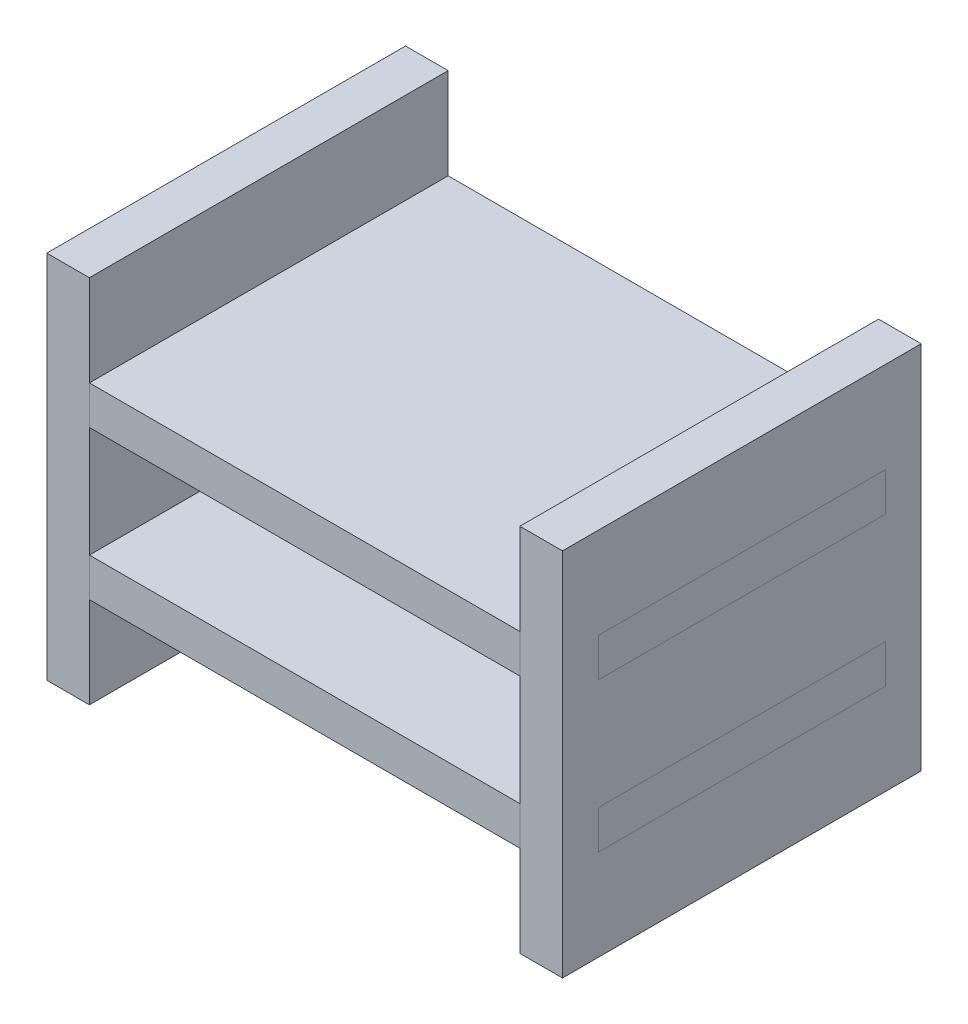
SolidWorks part; units mm, degrees
ref_plane "Front" through (0, 0, 0) normal (0, 0, 1) x (1, 0, 0)
ref_plane "Top" through (0, 0, 0) normal (0, 1, 0) x (1, 0, 0)
ref_plane "Right" through (0, 0, 0) normal (1, 0, 0) x (0, 0, -1)
sketch "Sketch2" plane through (0, 0, 0) normal (0, 1, 0) x (1, 0, 0)
  line L1 (-15, 12.5) -> (15, 12.5)
  line L2 (-15, 12.5) -> (-15, -12.5)
  line L3 (-15, -12.5) -> (15, -12.5)
  line L4 (15, 12.5) -> (15, -12.5)
  line L5 (-15, 12.5) -> (15, -12.5) construction
  line L6 (-15, -12.5) -> (15, 12.5) construction
  line L7 (-15, 10) -> (-17.97, 10)
  line L8 (-15, 10) -> (-15, -10)
  line L9 (-15, -10) -> (-17.97, -10)
  line L10 (-17.97, 10) -> (-17.97, -10)
  line L11 (-15, 10) -> (-17.97, -10) construction
  line L12 (-15, -10) -> (-17.97, 10) construction
  line L13 (15, 10) -> (17.97, 10)
  line L14 (15, 10) -> (15, -10)
  line L15 (15, -10) -> (17.97, -10)
  line L16 (17.97, 10) -> (17.97, -10)
  line L17 (15, 10) -> (17.97, -10) construction
  line L18 (15, -10) -> (17.97, 10) construction
  point P4 (0, 0)
  point P11 (-16.485, 0)
  point P16 (16.485, 0)
  dimension "D1" = 2.97
  dimension "D2" = 30
  dimension "D3" = 25
  dimension "D4" = 20
extrude "Boss-Extrude3" add sketch "Sketch2" along normal blind 2.69 contours L4 L1 L2 L3 | L7 L10 L9 L2 | L16 L13 L4 L15 region at (0, 0, 0) region at (-16.485, 0, 0) region at (16.485, 0, 0)
extrude "Boss-Extrude4" add sketch "Sketch2<3>" along normal blind 2.69 from offset 10.39 separate body contours L7 L10 L9 L2 | L4 L1 L2 L3 | L16 L13 L4 L15 region at (0, 0, 0) region at (-16.485, 0, 0) region at (16.485, 0, 0)
sketch "Sketch2<3>" plane through (0, 0, 0) normal (0, 1, 0) x (1, 0, 0) same geometry as "Sketch2"
sketch "Sketch4" plane through (15, 0, 0) normal (1, 0, 0) x (0, 0, -1)
  line L0 (0, 50) -> (0, -50) construction
  line L1 (12.5, -6.35) -> (-12.5, -6.35)
  line L2 (12.5, -6.35) -> (12.5, 19.43)
  line L3 (12.5, 19.43) -> (-12.5, 19.43)
  line L4 (-12.5, -6.35) -> (-12.5, 19.43)
  line L5 (12.5, -6.35) -> (-12.5, 19.43) construction
  line L6 (12.5, 19.43) -> (-12.5, -6.35) construction
  line L7 (-12.5, 13.08) -> (-12.5, 10.39) construction
  line L8 (-10, 13.08) -> (-12.5, 13.08) construction
  line L9 (0, 10.39) -> (0, 2.69) construction
  line L10 (10, 10.39) -> (-10, 10.39) construction
  line L11 (10, 2.69) -> (-10, 2.69) construction
  line L12 (-10, 13.08) -> (-10, 10.39) construction
  line L13 (-10, 13.08) -> (10, 13.08)
  line L14 (-10, 13.08) -> (-10, 10.39)
  line L15 (-10, 10.39) -> (10, 10.39)
  line L16 (10, 13.08) -> (10, 10.39)
  line L17 (-10, 13.08) -> (10, 10.39) construction
  line L18 (-10, 10.39) -> (10, 13.08) construction
  line L19 (10, 13.08) -> (-10, 13.08) construction
  line L21 (10, 2.69) -> (-10, 2.69)
  line L22 (10, 2.69) -> (10, 0)
  line L23 (10, 0) -> (-10, 0)
  line L24 (-10, 2.69) -> (-10, 0)
  line L25 (10, 2.69) -> (-10, 0) construction
  line L26 (10, 0) -> (-10, 2.69) construction
  point P0 (0, 6.54)
  point P19 (0, 6.54)
  point P22 (0, 11.735)
  point P32 (0, 1.345)
  dimension "D1" = 6.35
extrude "Boss-Extrude5" add sketch "Sketch4" along normal up to surface (2.97 mm away) separate body up to face at (17.97, 11.735, 0)
mirror "Mirror1" about plane through (0, 0, 0) normal (1, 0, 0) of bodies 105
